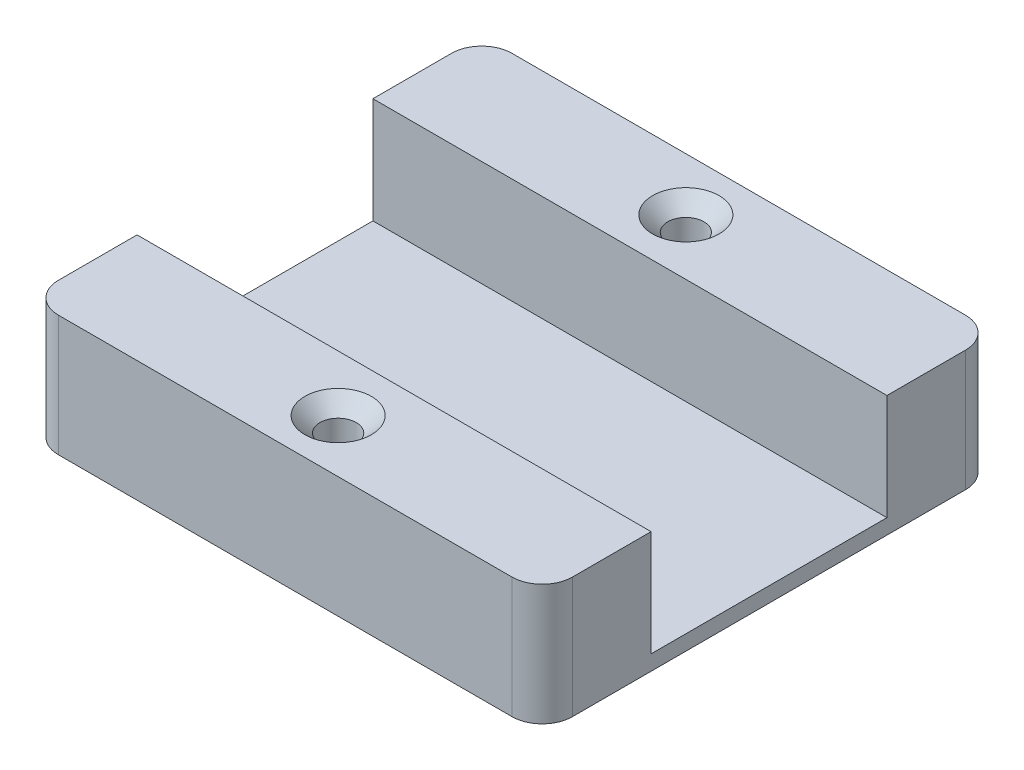
SolidWorks part; units mm, degrees
ref_plane "Front Plane" through (0, 0, 0) normal (0, 0, 1) x (1, 0, 0)
ref_plane "Top Plane" through (0, 0, 0) normal (0, 1, 0) x (1, 0, 0)
ref_plane "Right Plane" through (0, 0, 0) normal (1, 0, 0) x (0, 0, -1)
sketch "Sketch1" plane through (0, 0, 0) normal (0, 1, 0) x (1, 0, 0)
  line L0 (17, 4.7) -> (17, 15)
  line L1 (0, 0) -> (17, 0)
  line L2 (0, 0) -> (0, 15)
  line L3 (0, 15) -> (17, 15)
  line L4 (17, 0) -> (17, 2.3)
  arc A0 (17, 4.7) -> (17, 2.3) centre (17, 3.5) ccw
  dimension "D1" = 2.4
  dimension "D2" = 3.5
  dimension "D3" = 15
  dimension "D4" = 17
extrude "Boss-Extrude1" add sketch "Sketch1" along normal blind 8
sketch "Sketch2" plane through (17, 0, 0) normal (1, 0, 0) x (0, 0, -1)
  line L0 (4.7, 0) -> (15, 0) construction
  line L1 (15, 8) -> (7.2, 8)
  line L2 (15, 8) -> (15, 1)
  line L3 (15, 1) -> (7.2, 1)
  line L4 (7.2, 8) -> (7.2, 1)
  dimension "D1" = 1
  dimension "D2" = 7.8
extrude "Cut-Extrude1" cut sketch "Sketch2" against normal through all
chamfer "Chamfer1" distance 1 angle 45 1 edges at (15.8, 8, -3.5)
mirror "Mirror1" about plane through (17, 8, -4.7) normal (-1, 0, 0) of bodies 102
mirror "Mirror2" about plane through (0, 8, -15) normal (0, 0, 1) of bodies 103
fillet "Fillet1" radius 2 4 edges at (34, 4, -30) (0, 4, 0) (0, 4, -30) (34, 4, 0)
